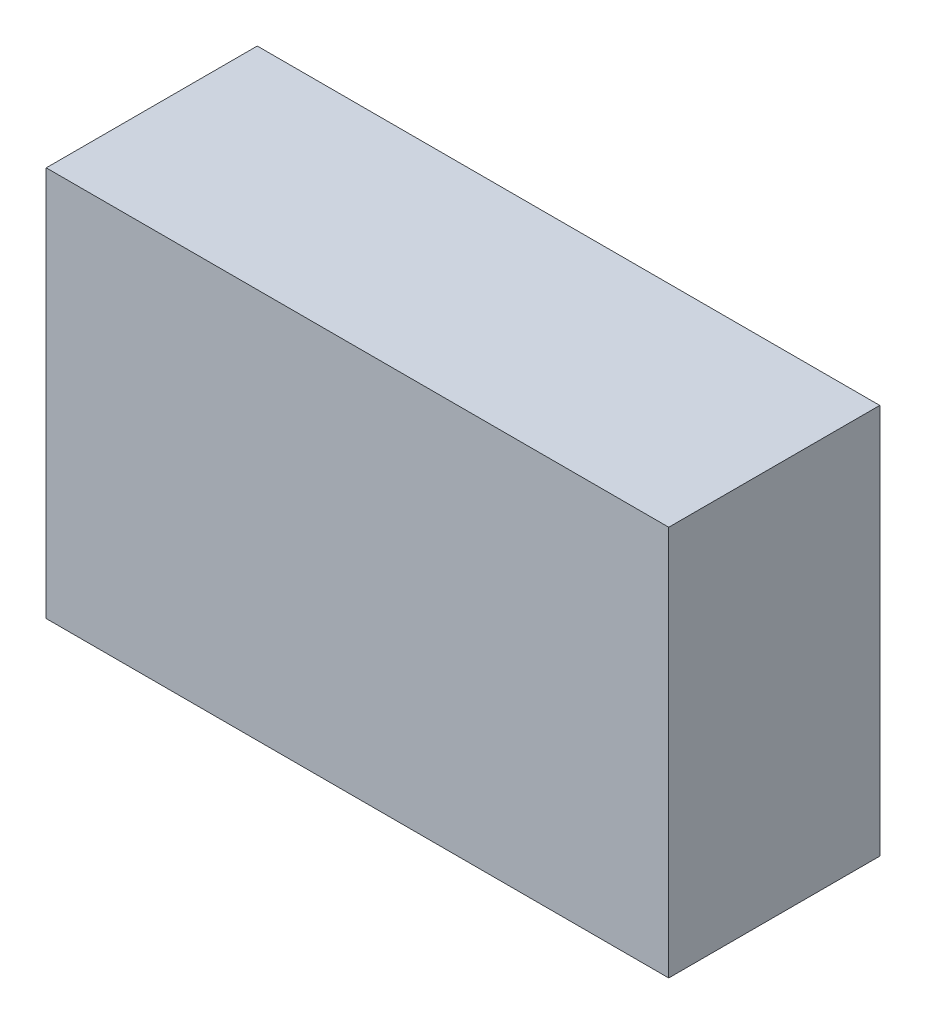
SolidWorks part; units mm, degrees
ref_plane "Front" through (0, 0, 0) normal (0, 0, 1) x (1, 0, 0)
ref_plane "Top" through (0, 0, 0) normal (0, 1, 0) x (1, 0, 0)
ref_plane "Right" through (0, 0, 0) normal (1, 0, 0) x (0, 0, -1)
sketch "Sketch1" plane through (0, 0, 0) normal (0, 1, 0) x (1, 0, 0)
  line L1 (0, 0) -> (149.86, 0)
  line L2 (0, 0) -> (0, 50.8)
  line L3 (0, 50.8) -> (149.86, 50.8)
  line L4 (149.86, 0) -> (149.86, 50.8)
  dimension "D1" = 149.86
  dimension "D2" = 50.8
extrude "Boss-Extrude1" add sketch "Sketch1" along normal blind 93.98
